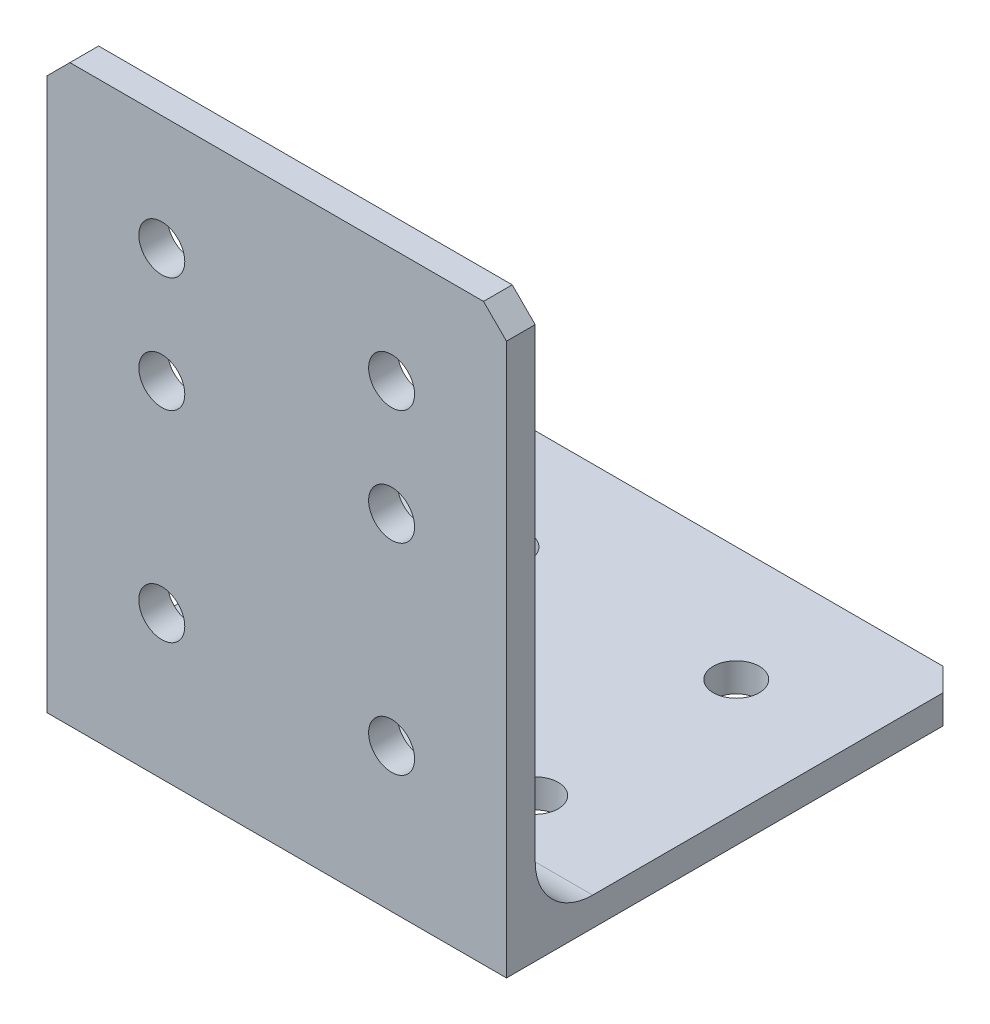
SolidWorks part; units mm, degrees
ref_plane "Front Plane" through (0, 0, 0) normal (0, 0, 1) x (1, 0, 0)
ref_plane "Top Plane" through (0, 0, 0) normal (0, 1, 0) x (1, 0, 0)
ref_plane "Right Plane" through (0, 0, 0) normal (1, 0, 0) x (0, 0, -1)
sketch "Sketch1" plane through (0, 0, 0) normal (1, 0, 0) x (0, 0, -1)
  line L0 (0, 0) -> (0, 63.5)
  line L1 (0, 63.5) -> (3.175, 63.5)
  line L2 (3.175, 63.5) -> (3.175, 3.175)
  line L3 (3.175, 3.175) -> (50.8, 3.175)
  line L4 (50.8, 3.175) -> (50.8, 0)
  line L5 (50.8, 0) -> (0, 0)
  dimension "D1" = 63.5
  dimension "D2" = 3.175
  dimension "D3" = 50.8
extrude "Boss-Extrude1" add sketch "Sketch1" along normal blind 50.8
sketch "Sketch2" plane through (0, 0, 0) normal (0, 0, 1) x (1, 0, 0)
  line L2 (50.8, 0) -> (0, 0) construction
  line L4 (25.4, 0) -> (25.4, 63.5) construction
  line L5 (50.8, 63.5) -> (0, 63.5) construction
  circle A0 centre (12.7, 38.1) radius 2.54
  circle A1 centre (12.7, 15.875) radius 2.54
  circle A6 centre (12.7, 50.8) radius 2.54
  circle A7 centre (38.1, 50.8) radius 2.54
  circle A8 centre (38.1, 15.875) radius 2.54
  circle A9 centre (38.1, 38.1) radius 2.54
  point P8 (0, 0)
  dimension "D1" = 5.08
  dimension "D2" = 12.7
  dimension "D3" = 12.7
  dimension "D4" = 15.875
  dimension "D5" = 22.225
extrude "Cut-Extrude1" cut sketch "Sketch2" against normal through all
sketch "Sketch3" plane through (0, 0, 0) normal (0, -1, 0) x (1, 0, 0)
  line L0 (50.8, -50.8) -> (0, -50.8) construction
  line L1 (50.8, 0) -> (0, 0) construction
  line L2 (50.8, 0) -> (50.8, -50.8) construction
  line L3 (0, 0) -> (0, -50.8) construction
  circle A0 centre (38.1, -38.1) radius 2.54
  circle A1 centre (38.1, -15.875) radius 2.54
  circle A2 centre (12.7, -38.1) radius 2.54
  circle A3 centre (12.7, -15.875) radius 2.54
  dimension "D1" = 5.08
  dimension "D2" = 12.7
  dimension "D3" = 15.875
  dimension "D4" = 12.7
  dimension "D5" = 12.7
  dimension "D6" = 22.225
extrude "Cut-Extrude2" cut sketch "Sketch3" against normal through all
fillet "Fillet1" radius 6.35 1 edges at (25.4, 3.175, -3.175)
chamfer "Chamfer1" distance 2.54 angle 45 4 edges at (50.8, 63.5, -1.5875) (0, 63.5, -1.5875) (50.8, 1.5875, -50.8) (0, 1.5875, -50.8)
